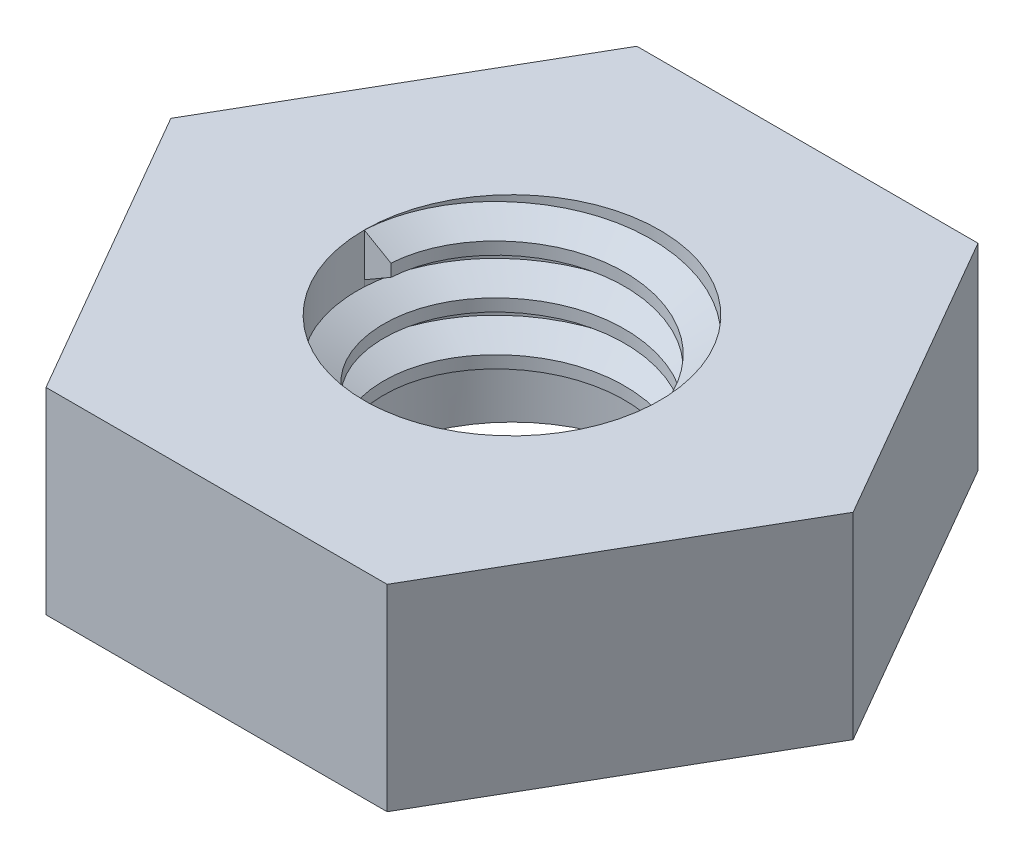
SolidWorks part; units mm, degrees
ref_plane "前基準面" through (0, 0, 0) normal (0, 0, 1) x (1, 0, 0)
ref_plane "上基準面" through (0, 0, 0) normal (0, 1, 0) x (1, 0, 0)
ref_plane "右基準面" through (0, 0, 0) normal (1, 0, 0) x (0, 0, -1)
sketch "草圖1" plane through (0, 0, 0) normal (0, 1, 0) x (1, 0, 0)
  line L1 (3.4641, 0) -> (1.7321, 3)
  line L2 (1.7321, 3) -> (-1.7321, 3)
  line L3 (-1.7321, 3) -> (-3.4641, 0)
  line L4 (-3.4641, 0) -> (-1.7321, -3)
  line L5 (-1.7321, -3) -> (1.7321, -3)
  line L6 (1.7321, -3) -> (3.4641, 0)
  circle A0 centre (0, 0) radius 3 construction
  circle A1 centre (0, 0) radius 1.5
  dimension "D2" = 3
  dimension "D1" = 6
extrude "填料-伸長1" add sketch "草圖1" along normal blind 2
thread "螺紋1" pitch 0.5 start angle 0, offset 0, length 0, pitch 0.5, diameter 3
ref_plane "平面1" through (-1.5, 2, 0) normal (0, 0, 1) x (-1, 0, 0)
sketch "螺紋輪廓1" plane through (-1.5, 2, 0) normal (0, 0, 1) x (-1, 0, 0)
  line L0 (0, 0) -> (0, 0.5) construction
  line L11 (0, 0) -> (0, 0.4375)
  line L12 (0, 0.4375) -> (-0.2706, 0.2812)
  line L13 (-0.2706, 0.2812) -> (-0.2706, 0.1562)
  line L15 (-0.2706, 0.1562) -> (0, 0)
  line L17 (-0.2706, 0.2187) -> (0, 0.2187) construction
  point P2 (0, 0)
  dimension "Pitch" = 0.5
  dimension "Profile_Angle" = 60
  dimension "Profile_Land" = 0.125
  dimension "Profile_Height" = 0.2706
